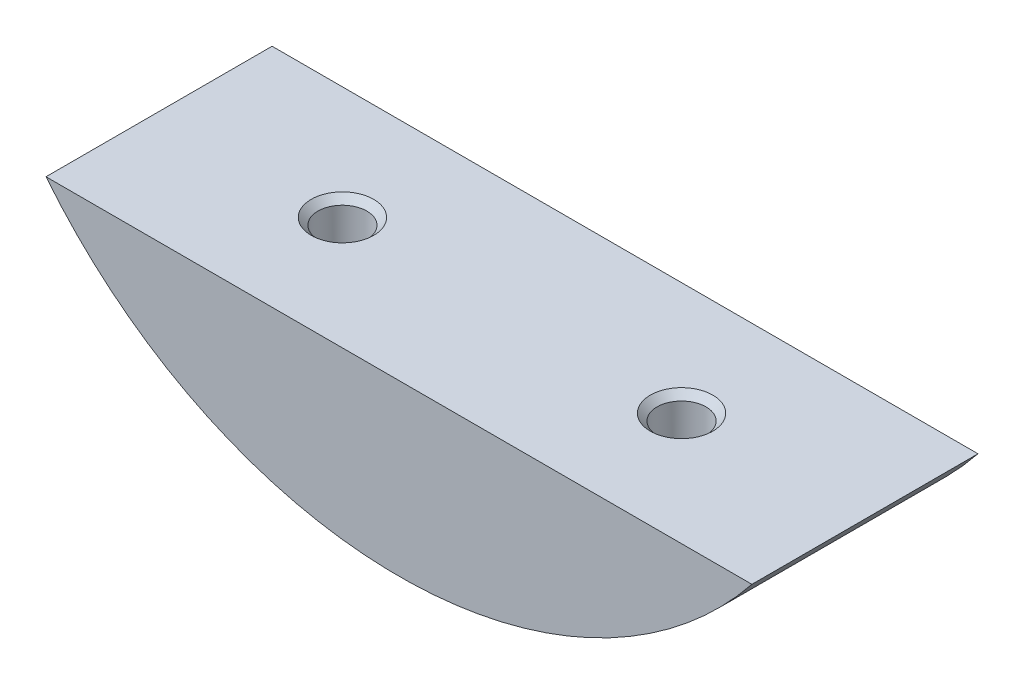
SolidWorks part; units mm, degrees
material "ABS"
ref_plane "Front Plane" through (0, 0, 0) normal (0, 0, 1) x (1, 0, 0)
ref_plane "Top Plane" through (0, 0, 0) normal (0, 1, 0) x (1, 0, 0)
ref_plane "Right Plane" through (0, 0, 0) normal (1, 0, 0) x (0, 0, -1)
sketch "Sketch1" plane through (0, 0, 0) normal (0, 0, 1) x (1, 0, 0)
  line L0 (0, 0) -> (79.3115, 0)
  arc A0 (0, 0) -> (79.3115, 0) centre (39.6557, 31.75) ccw
  dimension "D1" = 50.8
  dimension "D2" = 31.75
extrude "Boss-Extrude1" add sketch "Sketch1" along normal blind 25.4
sketch "Sketch2" plane through (0, 0, 0) normal (0, 1, 0) x (1, 0, 0)
  line L0 (0, -12.7) -> (20.6057, -12.7) construction
  line L1 (0, -25.4) -> (0, 0) construction
  line L2 (20.6057, -12.7) -> (58.7057, -12.7) construction
  line L3 (58.7057, -12.7) -> (79.3115, -12.7) construction
  line L4 (79.3115, -25.4) -> (79.3115, 0) construction
  circle A0 centre (20.6057, -12.7) radius 2
  circle A1 centre (58.7057, -12.7) radius 2
  dimension "D2" = 4
  dimension "D1" = 38.1
extrude "Cut-Extrude1" cut sketch "Sketch2" against normal through all both and the other way through all
sketch "Sketch3" plane through (0, 0, 0) normal (0, 1, 0) x (1, 0, 0)
  circle A0 centre (20.6057, -12.7) radius 2.75
  circle A1 centre (58.7057, -12.7) radius 2.75
  dimension "D1" = 5.5
extrude "Cut-Extrude2" cut sketch "Sketch3" against normal blind 5
chamfer "Chamfer1" distance 0.762 angle 45 2 edges at (20.6057, 0, 15.45) (58.7057, 0, 15.45)
